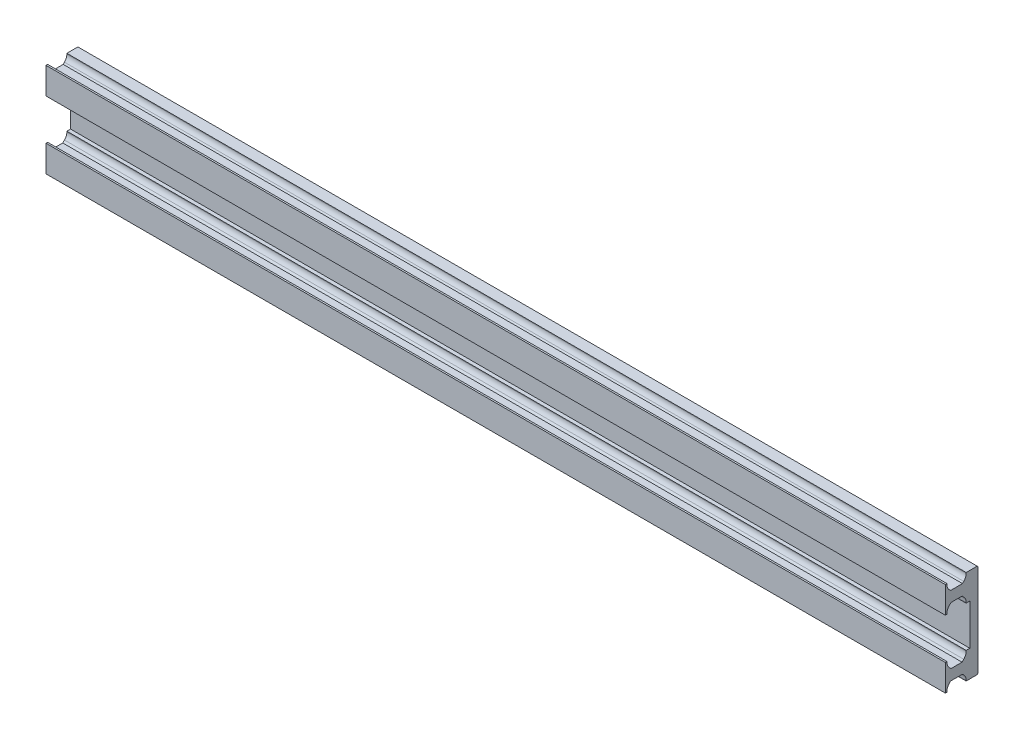
SolidWorks part; units mm, degrees
ref_plane "Front" through (0, 0, 0) normal (0, 0, 1) x (1, 0, 0)
ref_plane "Top" through (0, 0, 0) normal (0, 1, 0) x (1, 0, 0)
ref_plane "Right" through (0, 0, 0) normal (1, 0, 0) x (0, 0, -1)
sketch "Sketch1" plane through (0, 0, 0) normal (0, 0, 1) x (1, 0, 0)
  line L0 (-110, -4.5) -> (-110, 4.5) construction
  line L1 (110, 11.5) -> (-110, 11.5)
  line L2 (110, 11.5) -> (110, -11.5)
  line L3 (110, -11.5) -> (-110, -11.5)
  line L4 (-110, 11.5) -> (-110, -11.5)
  line L5 (110, 11.5) -> (-110, -11.5) construction
  line L6 (110, -11.5) -> (-110, 11.5) construction
  line L8 (110, 4.5) -> (-110, 4.5) construction
  point P0 (0, 0)
  dimension "D1" = 7
extrude "Boss-Extrude1" add sketch "Sketch1" against normal blind 2
sketch "Sketch2" plane through (0, 0, 0) normal (0, 0, 1) x (1, 0, 0)
  line L0 (-110, 11.5) -> (-110, -11.5) construction
  line L1 (110, 11.5) -> (-110, 11.5)
  line L2 (110, 11.5) -> (110, 5)
  line L3 (110, 5) -> (-110, 5)
  line L4 (-110, 11.5) -> (-110, 5)
  line L5 (110, -11.5) -> (110, 11.5) construction
  line L6 (110, -11.5) -> (-110, -11.5)
  line L7 (110, -11.5) -> (110, -5)
  line L8 (110, -5) -> (-110, -5)
  line L9 (-110, -11.5) -> (-110, -5)
  line L11 (110, 4.5) -> (-110, 4.5) construction
  dimension "D1" = 0.5
extrude "Boss-Extrude2" add sketch "Sketch2" along normal offset from surface (6 mm away) 1
ref_plane "Center of Slots" through (0, 8.25, 0) normal (0, -1, 0) x (-1, 0, 0)
sketch "Sketch5" plane through (0, 0, 0) normal (1, 0, 0) x (0, 0, -1)
  line L16 (-1.9, 7) -> (-4.6, 7)
  line L17 (-1.9, 7) -> (-4.6, 7)
  line L18 (-1.4858, 6.5858) -> (-1.9, 7)
  line L19 (-1.4858, 6.5858) -> (-1.9, 7)
  line L20 (-0.9, 4.3284) -> (-0.9, 5.1716)
  line L21 (-0.9, 4.3284) -> (-0.9, 5.1716)
  line L22 (-1.9, 2.5) -> (-1.4858, 2.9142)
  line L23 (-1.9, 2.5) -> (-1.4858, 2.9142)
  line L24 (-4.6, 2.5) -> (-1.9, 2.5)
  line L25 (-4.6, 2.5) -> (-1.9, 2.5)
  line L26 (-5.0142, 2.9142) -> (-4.6, 2.5)
  line L27 (-5.0142, 2.9142) -> (-4.6, 2.5)
  line L28 (-5.6, 5.1716) -> (-5.6, 4.3284)
  line L29 (-5.6, 5.1716) -> (-5.6, 4.3284)
  line L30 (-4.6, 7) -> (-5.0142, 6.5858)
  line L31 (-4.6, 7) -> (-5.0142, 6.5858)
  arc A12 (-0.9, 5.1716) -> (-1.4858, 6.5858) centre (-2.9, 5.1716) ccw
  arc A13 (-0.9, 5.1716) -> (-1.4858, 6.5858) centre (-2.9, 5.1716) ccw
  arc A14 (-1.4858, 2.9142) -> (-0.9, 4.3284) centre (-2.9, 4.3284) ccw
  arc A15 (-1.4858, 2.9142) -> (-0.9, 4.3284) centre (-2.9, 4.3284) ccw
  arc A16 (-5.6, 4.3284) -> (-5.0142, 2.9142) centre (-3.6, 4.3284) ccw
  arc A17 (-5.6, 4.3284) -> (-5.0142, 2.9142) centre (-3.6, 4.3284) ccw
  arc A18 (-5.0142, 6.5858) -> (-5.6, 5.1716) centre (-3.6, 5.1716) ccw
  arc A19 (-5.0142, 6.5858) -> (-5.6, 5.1716) centre (-3.6, 5.1716) ccw
  dimension "D1" = 0
extrude "Slot 1" cut sketch "Sketch5" against normal through all both and the other way through all
mirror "Slot 1x2" about plane through (0, 8.25, 0) normal (0, -1, 0) of "Slot 1"
mirror "Slot 2" about plane through (0, 0, 0) normal (0, 1, 0) of "Slot 1x2", "Slot 1"
chamfer "Deburs" distance 0.2 angle 45 2 edges at (0, -11.5, -2) (0, 11.5, -2)
sketch "Sketch6" plane through (0, 0, 0) normal (1, 0, 0) x (0, 0, -1)
  line L1 (-4.6, 9.5) -> (-5.0142, 9.9142) construction
  line L2 (-1.4858, 9.9142) -> (-1.9, 9.5) construction
  line L3 (-4.6, 9.5) -> (-4.7, 9.6)
  line L4 (-1.8, 9.6) -> (-1.9, 9.5)
  line L5 (-4.6, 9.5) -> (-1.9, 9.5)
  line L6 (-4.7, 9.6) -> (-1.8, 9.6)
  dimension "D1" = 0.1
extrude "Tighten Top Bearing Slot" add sketch "Sketch6" along normal through all and the other way through all
mirror "Tighten Top Bearing Mirror" about plane through (0, 0, 0) normal (0, 1, 0) of "Tighten Top Bearing Slot"
